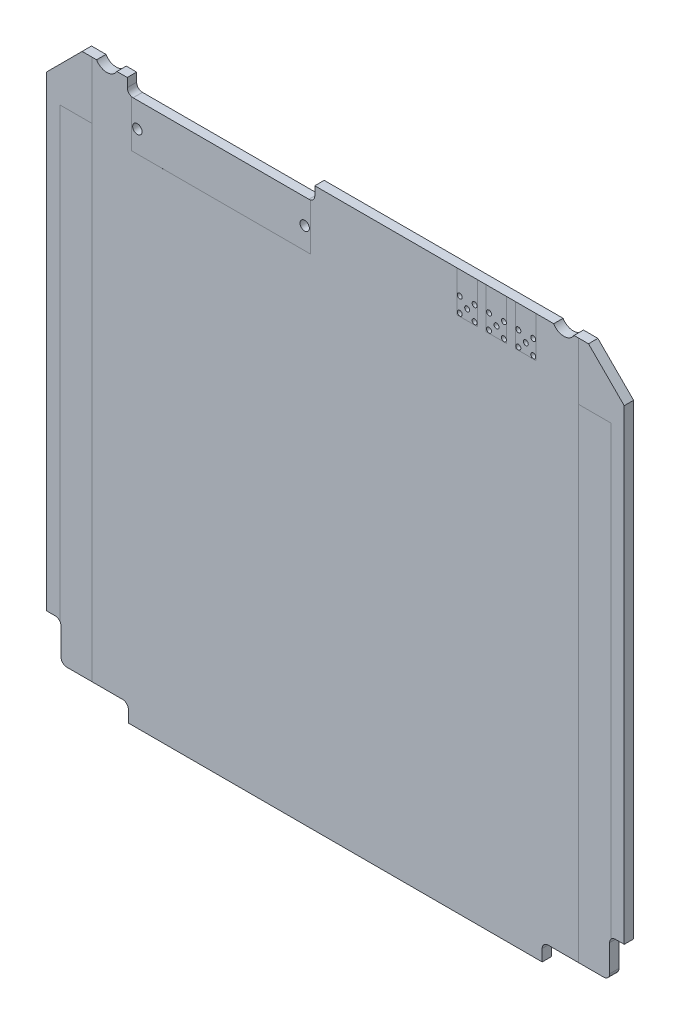
SolidWorks part; units mm, degrees
material "FR4_stuffedProtoboard"
ref_plane "Front Plane" through (0, 0, 0) normal (0, 0, 1) x (1, 0, 0)
ref_plane "Top Plane" through (0, 0, 0) normal (0, 1, 0) x (1, 0, 0)
ref_plane "Right Plane" through (0, 0, 0) normal (1, 0, 0) x (0, 0, -1)
ref_plane "Plane4" through (0, 0, -0.0125) normal (0, 0, -1) x (-1, 0, 0)
sketch "Sketch1" plane through (0, 0, -0.0125) normal (0, 0, -1) x (-1, 0, 0)
  line L0 (35.3, -50) -> (35.3, -48)
  line L1 (36.3, -47) -> (45.8, -47)
  line L2 (46.8, -46) -> (46.8, -41.4)
  line L3 (47.8, -40.4) -> (49.3, -40.4)
  line L4 (49.3, -40.4) -> (49.3, 39.2)
  line L5 (49.3, 39.2) -> (43.2, 45.3)
  line L6 (43.2, 45.3) -> (35.5, 45.3)
  line L7 (35.5, 45.3) -> (35.5, 43.8)
  line L8 (34.5, 42.8) -> (4.5, 42.8)
  line L9 (3.5, 43.8) -> (3.5, 45.3)
  line L10 (3.5, 45.3) -> (-43.2, 45.3)
  line L11 (-43.2, 45.3) -> (-49.3, 39.2)
  line L12 (-49.3, 39.2) -> (-49.3, -40.4)
  line L13 (-49.3, -40.4) -> (-47.8, -40.4)
  line L14 (-46.8, -41.4) -> (-46.8, -46)
  line L15 (-45.8, -47) -> (-36.3, -47)
  line L16 (-35.3, -48) -> (-35.3, -50)
  line L17 (-35.3, -50) -> (35.3, -50)
  line L18 (0, -50) -> (0, 45.3) construction
  line L19 (19.5, 42.8) -> (19.5, 25.5258) construction
  line L20 (-21.23, 41.37) -> (-23.77, 38.83) construction
  line L21 (-26.23, 41.37) -> (-28.77, 38.83) construction
  line L22 (-31.23, 41.37) -> (-33.77, 38.83) construction
  arc A0 (35.3, -48) -> (36.3, -47) centre (36.3, -48) cw
  arc A1 (45.8, -47) -> (46.8, -46) centre (45.8, -46) ccw
  arc A2 (46.8, -41.4) -> (47.8, -40.4) centre (47.8, -41.4) cw
  arc A3 (35.5, 43.8) -> (34.5, 42.8) centre (34.5, 43.8) cw
  arc A4 (4.5, 42.8) -> (3.5, 43.8) centre (4.5, 43.8) cw
  arc A5 (-47.8, -40.4) -> (-46.8, -41.4) centre (-47.8, -41.4) cw
  arc A6 (-46.8, -46) -> (-45.8, -47) centre (-45.8, -46) ccw
  arc A7 (-36.3, -47) -> (-35.3, -48) centre (-36.3, -48) cw
  circle A8 centre (-26.23, 41.37) radius 0.425
  circle A9 centre (-28.77, 41.37) radius 0.425
  circle A10 centre (-27.5, 40.1) radius 0.425
  circle A11 centre (-21.23, 41.37) radius 0.425
  circle A12 centre (-28.77, 38.83) radius 0.425
  circle A13 centre (-23.77, 41.37) radius 0.425
  circle A14 centre (-22.5, 40.1) radius 0.425
  circle A15 centre (-26.23, 38.83) radius 0.425
  circle A16 centre (-31.23, 41.37) radius 0.425
  circle A17 centre (-33.77, 41.37) radius 0.425
  circle A18 centre (-23.77, 38.83) radius 0.425
  circle A19 centre (-32.5, 40.1) radius 0.425
  circle A20 centre (-33.77, 38.83) radius 0.425
  circle A21 centre (-31.23, 38.83) radius 0.425
  circle A22 centre (33.775, 38.54) radius 0.8
  circle A23 centre (5.225, 38.54) radius 0.8
  circle A24 centre (-21.23, 38.83) radius 0.425
  point P35 (-22.5, 40.1)
  dimension "D7" = 2.5
  dimension "D8" = 1.6
  dimension "D9" = 14.275
  dimension "D10" = 4.26
  dimension "D11" = 1
  dimension "D12" = 1
  dimension "D13" = 1
  dimension "D14" = 1
  dimension "D15" = 1
  dimension "D16" = 1
  dimension "D17" = 1
  dimension "D18" = 1
  dimension "D26" = 0.85
  dimension "D1" = 98.6
  dimension "D2" = 95.3
  dimension "D3" = 14
  dimension "D4" = 9.6
  dimension "D5" = 2.5
  dimension "D6" = 3
  dimension "D19" = 14
  dimension "D20" = 2.5
  dimension "D21" = 6.1
  dimension "D22" = 6.1
  dimension "D23" = 32
  dimension "D24" = 2.54
  dimension "D25" = 2.54
  dimension "D28" = 5
  dimension "D29" = 3.93
  dimension "D30" = 28.07
  dimension "D31" = 45
  dimension "D32" = 45
  dimension "D33" = 29.8
  dimension "D34" = 50
  dimension "D27" = 3
extrude "Boss-Extrude1" add sketch "Sketch1" against normal blind 1.6
sketch "thermalContacts_lower" plane through (0, 0, -0.0125) normal (0, 0, -1) x (-1, 0, 0)
  line L3 (47, 35.5) -> (47, -41.5)
  line L4 (41.5, 35.5) -> (41.5, 41.5)
  line L5 (41.5, 35.5) -> (47, 35.5)
  line L9 (-47, 35.5) -> (-47, -41.1726)
  line L10 (-41.5, 35.5) -> (-47, 35.5)
  line L11 (-41.5, 35.5) -> (-41.5, 42.5522)
  line L14 (-41.5, 42.5522) -> (-41.5, 47.8583)
  line L18 (41.5, 41.5) -> (41.5, 47)
  line L20 (47, -41.5) -> (59.8273, -41.5)
  line L21 (59.8273, -41.5) -> (59.8273, 47)
  line L22 (-54.1782, 47.8583) -> (-41.5, 47.8583)
  line L23 (41.5, 47) -> (59.8273, 47)
  line L24 (-54.1782, 47.8583) -> (-54.1782, -41.1726)
  line L25 (-47, -41.1726) -> (-54.1782, -41.1726)
  line L26 (43.2, 45.3) -> (35.5, 45.3) construction
  line L27 (49.3, -40.4) -> (49.3, 39.2) construction
  line L28 (3.5, 45.3) -> (-43.2, 45.3) construction
  line L29 (-49.3, 39.2) -> (-49.3, -40.4) construction
  dimension "D1" = 9.8
  dimension "D2" = 7.8
  dimension "D3" = 2.3
  dimension "D4" = 9.8
  dimension "D5" = 7.8
  dimension "D6" = 2.3
sketch "thermalContacts_upper" plane through (0, 0, 1.5875) normal (0, 0, 1) x (1, 0, 0)
  line L3 (-47, 35.5) -> (-47, -41.5)
  line L4 (-41.5, 35.5) -> (-41.5, 41.5)
  line L5 (-41.5, 35.5) -> (-47, 35.5)
  line L9 (47, 35.5) -> (47, -41.5)
  line L10 (41.5, 35.5) -> (47, 35.5)
  line L11 (41.5, 35.5) -> (41.5, 41.5)
  line L14 (41.5, 41.5) -> (41.5, 47)
  line L15 (41.5, 41.5) -> (49.5, 41.5) construction
  line L18 (-41.5, 41.5) -> (-41.5, 47)
  line L19 (-41.5, 41.5) -> (-49.5, 41.5) construction
  line L20 (47, -41.5) -> (59.8273, -41.5)
  line L21 (59.8273, -41.5) -> (59.8273, 47)
  line L22 (59.8273, 47) -> (41.5, 47)
  line L23 (-41.5, 47) -> (-56.1922, 47)
  line L24 (-56.1922, 47) -> (-56.1922, -41.5)
  line L25 (-56.1922, -41.5) -> (-47, -41.5)
extrude "keepOut_top" cut sketch "thermalContacts_lower" against normal blind 0.0001
extrude "keepOut_bottom" cut sketch "thermalContacts_upper" against normal blind 0.0001
sketch "partFootprints" plane through (0, 0, 1.5875) normal (0, 0, 1) x (1, 0, 0)
  line L0 (-34.74, 34.84) -> (-34.74, 42.8292)
  line L1 (-4.26, 34.84) -> (-34.74, 34.84)
  line L2 (-41.5, 45.3) -> (-35.5, 45.3) construction
  line L3 (-36.1132, 45.3) -> (-39.5054, 45.3) construction
  line L4 (-4.26, 34.84) -> (-4.26, 42.8292)
  line L5 (-49.3, -40.4) -> (-49.3, 39.2) construction
  line L6 (20.75, 45.3) -> (20.75, 38.35)
  line L7 (20.75, 38.35) -> (24.25, 38.35)
  line L8 (24.25, 38.35) -> (24.25, 45.3)
  line L9 (24.25, 45.3) -> (20.75, 45.3)
  line L10 (25.75, 45.3) -> (25.75, 38.35)
  line L11 (25.75, 38.35) -> (29.25, 38.35)
  line L12 (29.25, 38.35) -> (29.25, 45.3)
  line L13 (29.25, 45.3) -> (25.75, 45.3)
  line L14 (30.75, 45.3) -> (30.75, 38.35)
  line L15 (30.75, 38.35) -> (34.25, 38.35)
  line L16 (34.25, 38.35) -> (34.25, 45.3)
  line L17 (34.25, 45.3) -> (30.75, 45.3)
  line L19 (32.5, 38.35) -> (32.5, 40.1) construction
  line L20 (-34.74, 42.8292) -> (-4.26, 42.8292)
  line L21 (-3.5, 45.3) -> (41.5, 45.3) construction
  line L22 (14.12, 38.35) -> (15.8235, 38.35) construction
  line L23 (22.5, 38.35) -> (22.5, 40.1) construction
  line L25 (20.75, 42.2411) -> (20.75, 38.35) construction
  line L26 (24.25, 41.85) -> (24.25, 38.35) construction
  arc A0 (-35.5, 43.8) -> (-34.5, 42.8) centre (-34.5, 43.8) ccw construction
  arc A1 (-4.5, 42.8) -> (-3.5, 43.8) centre (-4.5, 43.8) ccw construction
  circle A3 centre (32.5, 40.1) radius 0.425 construction
  circle A4 centre (22.5, 40.1) radius 0.425 construction
  point P35 (0, 0)
  dimension "D1" = 10.46
  dimension "D2" = 14.56
  dimension "D3" = 30.48
  dimension "D4" = 6.95
  dimension "D8" = 3.5
  dimension "D6" = 3
extrude "footPrints" cut sketch "partFootprints" against normal blind 0.0001
sketch "Sketch3" plane through (0, 0, 1.5875) normal (0, 0, 1) x (1, 0, 0)
  line L1 (41.5, -47) -> (41.5, 35.5)
  line L2 (47, 35.5) -> (47, -40.8) construction
  line L3 (46.8, -41.4) -> (46.8, -46) construction
  line L4 (45.8, -47) -> (36.3, -47) construction
  line L5 (47, 35.5) -> (47, -40.8)
  line L6 (46.8, -41.4) -> (46.8, -46)
  line L7 (45.8, -47) -> (41.5, -47)
  line L8 (41.5, 35.5) -> (47, 35.5) construction
  line L9 (41.5, 35.5) -> (47, 35.5)
  line L10 (0, -50) -> (0, 45.3) construction
  line L11 (35.3, -50) -> (-35.3, -50) construction
  line L12 (-3.5, 45.3) -> (20.75, 45.3) construction
  line L13 (-41.5, 35.5) -> (-47, 35.5)
  line L14 (-45.8, -47) -> (-41.5, -47)
  line L15 (-46.8, -41.4) -> (-46.8, -46)
  line L16 (-47, 35.5) -> (-47, -40.8)
  line L17 (-41.5, -47) -> (-41.5, 35.5)
  line L18 (41.5, 45.3) -> (41.5, 35.5) construction
  arc A0 (47, -40.8) -> (46.8, -41.4) centre (47.8, -41.4) ccw construction
  arc A1 (45.8, -47) -> (46.8, -46) centre (45.8, -46) ccw construction
  arc A2 (47, -40.8) -> (46.8, -41.4) centre (47.8, -41.4) ccw
  arc A3 (45.8, -47) -> (46.8, -46) centre (45.8, -46) ccw
  arc A4 (-45.8, -47) -> (-46.8, -46) centre (-45.8, -46) cw
  arc A5 (-47, -40.8) -> (-46.8, -41.4) centre (-47.8, -41.4) cw
extrude "caution_top" cut sketch "Sketch3" against normal blind 0.0001
ref_plane "midplane_Z" through (0, 0, 0.7875) normal (0, 0, 1) x (1, 0, 0)
mirror "caution_bottom" about plane through (0, 0, 0.7875) normal (0, 0, 1) of "caution_top"
ref_point "rail midpoint"
sketch "Sketch4" plane through (0, 0, 1.5875) normal (0, 0, 1) x (1, 0, 0)
  line L0 (34.25, 45.3) -> (41.5, 45.3) construction
  line L1 (37.2679, 45.3) -> (40.7321, 45.3)
  line L2 (0, -50) -> (0, 45.3) construction
  line L3 (-37.2679, 45.3) -> (-40.7321, 45.3)
  line L4 (41.5, 45.3) -> (41.5, -47) construction
  line L5 (35.3, -50) -> (-35.3, -50) construction
  line L6 (-3.5, 45.3) -> (20.75, 45.3) construction
  arc A0 (40.7321, 45.3) -> (37.2679, 45.3) centre (39, 46.3) cw
  arc A1 (-40.7321, 45.3) -> (-37.2679, 45.3) centre (-39, 46.3) ccw
  point P5 (39, 44.3)
  point P16 (40.5773, 45.3)
  dimension "D1" = 2
  dimension "D2" = 1
  dimension "D3" = 2.5
extrude "Cut-Extrude2" cut sketch "Sketch4" against normal through all both and the other way through all
